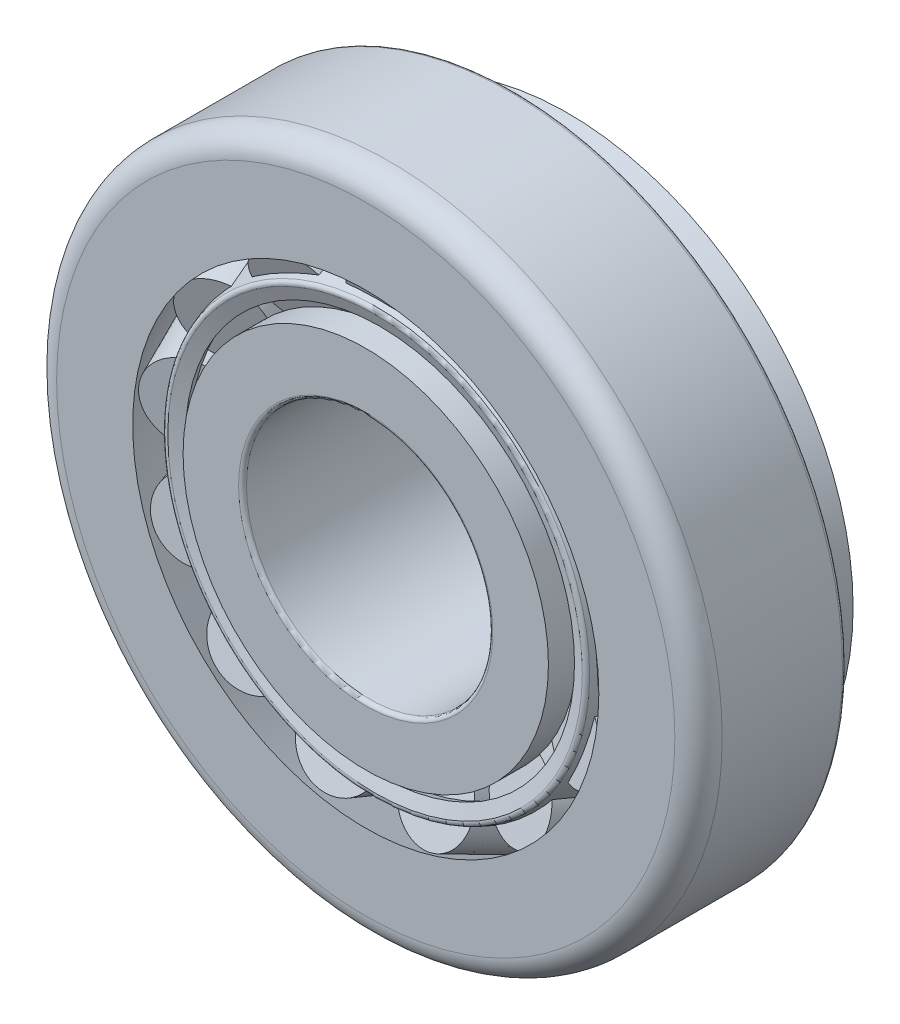
SolidWorks part; units mm, degrees
ref_plane "Front Plane" through (0, 0, 0) normal (0, 0, 1) x (1, 0, 0)
ref_plane "Top Plane" through (0, 0, 0) normal (0, 1, 0) x (1, 0, 0)
ref_plane "Right Plane" through (0, 0, 0) normal (1, 0, 0) x (0, 0, -1)
sketch "Sketch1" plane through (0, 0, 0) normal (1, 0, 0) x (0, 0, -1)
  line L0 (-4.7625, 21.4313) -> (-4.7625, 15.01)
  line L1 (-4.7625, 15.01) -> (4.7625, 19.47)
  line L2 (4.7625, 19.47) -> (4.7625, 21.4313)
  line L3 (4.7625, 21.4313) -> (-4.7625, 21.4313)
  line L4 (0, 0) -> (10110.1541, 0) construction
  line L5 (0.1497, 17.3101) -> (8.255, 0) construction
  line L6 (9.525, 14.9) -> (9.525, 7.9375)
  line L7 (9.525, 7.9375) -> (-4.7625, 7.9375)
  line L8 (-4.7625, 7.9375) -> (-4.7625, 11.765)
  line L9 (-4.7625, 11.765) -> (-2.8992, 11.765)
  line L10 (9.525, 14.9) -> (5.902, 14.9)
  line L12 (9.525, 21.4313) -> (-4.2545, 21.4313) construction
  line L14 (-4.2545, 13.5832) -> (8.24, 18.384)
  line L15 (8.24, 18.384) -> (8.509, 17.6839)
  line L16 (8.509, 17.6839) -> (-3.2854, 13.1521)
  line L17 (-3.2854, 13.1521) -> (-3.1509, 12.8021)
  line L18 (-4.24, 15.2546) -> (4.24, 19.2254) construction
  line L19 (-4.2545, 13.5832) -> (-3.851, 12.5331)
  line L20 (-3.851, 12.5331) -> (-3.1509, 12.8021)
  line L21 (4.24, 19.2254) -> (6.5498, 13.2138)
  line L22 (6.5498, 13.2138) -> (-2.4072, 10.4846)
  line L23 (-2.4072, 10.4846) -> (-4.24, 15.2546)
  line L25 (-3.3236, 12.8696) -> (5.3949, 16.2196) construction
  line L27 (0, 17.24) -> (1.0357, 14.5446) construction
  line L28 (1.0357, 14.5446) -> (2.0713, 11.8492) construction
  line L29 (-4.2545, 21.4313) -> (-4.2545, 13.5832) construction
  point P7 (0, 21.4313)
  point P44 (5.3053, 16.453)
  dimension "Width" = 9.525
  dimension "Inner Ring Width" = 14.2875
  dimension "D17" = 0.375
  dimension "D2" = 0.25
  dimension "D3" = 13.7795
  dimension "ID" = 15.875
  dimension "OD" = 42.8625
  dimension "Cage Width" = 13.7795
sketch "Sketch0" plane through (0, 0, 0) normal (0, 0, 1) x (1, 0, 0)
  circle A0 centre (0, 0) radius 7.9375
  circle A1 centre (0, 0) radius 21.4313
  dimension "D1" = 42.8625
  dimension "D2" = 15.875
sketch "Sketch2" plane through (0, 0, 0) normal (1, 0, 0) x (0, 0, -1)
  line L0 (-4.7625, 21.4313) -> (-4.7625, 15.01)
  line L1 (-4.7625, 15.01) -> (4.7625, 19.47)
  line L2 (4.7625, 19.47) -> (4.7625, 21.4313)
  line L3 (4.7625, 21.4313) -> (-4.7625, 21.4313)
revolve "Revolve1" add sketch "Sketch2" angle 360 about L4
sketch "Sketch3" plane through (0, 0, 0) normal (1, 0, 0) x (0, 0, -1)
  line L0 (-4.7625, 11.765) -> (-4.7625, 7.9375)
  line L1 (-4.7625, 7.9375) -> (9.525, 7.9375)
  line L2 (9.525, 7.9375) -> (9.525, 14.9)
  line L3 (9.525, 14.9) -> (5.902, 14.9)
  line L4 (5.902, 14.9) -> (6.5498, 13.2138)
  line L5 (6.5498, 13.2138) -> (-2.4072, 10.4846)
  line L6 (-2.4072, 10.4846) -> (-2.8992, 11.765)
  line L7 (-2.8992, 11.765) -> (-4.7625, 11.765)
revolve "Revolve2" add sketch "Sketch3" angle 360 about L4
sketch "Sketch4" plane through (0, 0, 0) normal (1, 0, 0) x (0, 0, -1)
  line L0 (8.509, 17.6839) -> (8.24, 18.384)
  line L1 (8.24, 18.384) -> (-4.2545, 13.5832)
  line L2 (-4.2545, 13.5832) -> (-3.851, 12.5331)
  line L3 (-3.851, 12.5331) -> (-3.1509, 12.8021)
  line L4 (-3.1509, 12.8021) -> (-3.2854, 13.1521)
  line L5 (-3.2854, 13.1521) -> (8.509, 17.6839)
revolve "Revolve3" add sketch "Sketch4" angle 360 about L4
sketch "Sketch6" plane through (0, 0, 0) normal (1, 0, 0) x (0, 0, -1)
  line L0 (6.5498, 13.2138) -> (5.3949, 16.2196)
  line L1 (5.3949, 16.2196) -> (-3.3236, 12.8696)
  line L3 (-3.3236, 12.8696) -> (-2.4072, 10.4846)
  line L4 (-2.4072, 10.4846) -> (6.5498, 13.2138)
  line L5 (-3.3236, 12.8696) -> (5.3949, 16.2196) construction
  line L6 (-2.4072, 10.4846) -> (-4.24, 15.2546) construction
revolve "Revolve4" add sketch "Sketch6" angle 360 about L25
pattern_circular "CirPattern1" count 13 over 360 about axis through (0, 0, 0) along (0, 0, -1) of "Revolve4"
fillet "Fillet1" radius 1.524 1 edges at (7.9375, 0, -9.525)
fillet "Fillet2" radius 1.524 1 edges at (21.4313, 0, 4.7625)
fillet "Fillet3" radius 0.254 1 edges at (7.9375, 0, 4.7625)
fillet "Fillet4" radius 0.254 1 edges at (21.4313, 0, -4.7625)
fillet "Fillet5" radius 0.254 1 edges at (13.5832, 0, 4.2545)
sketch "Sketch7" plane through (0, 0, 0) normal (1, 0, 0) x (0, 0, -1)
  line L0 (9.525, 14.9) -> (9.525, 7.9375) construction
  line L1 (-4.7625, 11.765) -> (-2.8992, 11.765) construction
  line L2 (-4.7625, 7.9375) -> (-4.7625, 11.765) construction
  line L3 (9.525, 7.9375) -> (-4.7625, 7.9375) construction
  line L4 (9.525, 14.9) -> (5.902, 14.9) construction
  line L5 (6.5498, 13.2138) -> (-2.4072, 10.4846) construction
  line L6 (4.24, 19.2254) -> (6.5498, 13.2138) construction
  line L7 (-4.7625, 15.01) -> (4.7625, 19.47) construction
  line L8 (-2.4072, 10.4846) -> (-4.24, 15.2546) construction
  line L9 (9.525, 14.9) -> (9.525, 7.9375)
  line L10 (-4.7625, 11.765) -> (-2.8992, 11.765)
  line L11 (-4.7625, 7.9375) -> (-4.7625, 11.765)
  line L12 (9.525, 7.9375) -> (-4.7625, 7.9375)
  line L13 (9.525, 14.9) -> (5.902, 14.9)
  line L14 (6.5498, 13.2138) -> (-2.4072, 10.4846)
  line L15 (4.24, 19.2254) -> (6.5498, 13.2138)
  line L16 (-4.24, 15.2546) -> (4.24, 19.2254)
  line L17 (-2.4072, 10.4846) -> (-4.24, 15.2546)
  line L18 (0, 0) -> (-4.0174, 0) construction
  line L19 (-200000, 0) -> (210110.1541, 0) construction
  line L20 (-4.0174, -13.6743) -> (-4.0174, 13.6743) construction
  line L21 (-2.4072, -10.4846) -> (-4.24, -15.2546)
  line L22 (-4.24, -15.2546) -> (4.24, -19.2254)
  line L23 (4.24, -19.2254) -> (6.5498, -13.2138)
  line L24 (6.5498, -13.2138) -> (-2.4072, -10.4846)
  line L25 (9.525, -14.9) -> (5.902, -14.9)
  line L26 (9.525, -7.9375) -> (-4.7625, -7.9375)
  line L27 (-4.7625, -7.9375) -> (-4.7625, -11.765)
  line L28 (-4.7625, -11.765) -> (-2.8992, -11.765)
  line L29 (9.525, -14.9) -> (9.525, -7.9375)
move or copy body "Body-Move/Copy1" [suppressed] bodies to move or copy 104 copy no translate (0, 0, 33.3375)
ref_plane "Contact Plane 1" through (0, 0, 4.7625) normal (0, 0, 1) x (1, 0, 0)
ref_plane "Contact Plane 2" through (0, 0, -4.7625) normal (0, 0, -1) x (-1, 0, 0)
ref_axis "Center Axis 1" through (0, 0, -8.001) along (0, 0, 1)
equation "\"D17@Sketch1\" = \"Cone Thick@Sketch1\" / 2"
equation "\"D1@Fillet4\"=\"D1@Fillet3\""
equation "\"D1@Fillet5\"=\"D1@Fillet4\""
